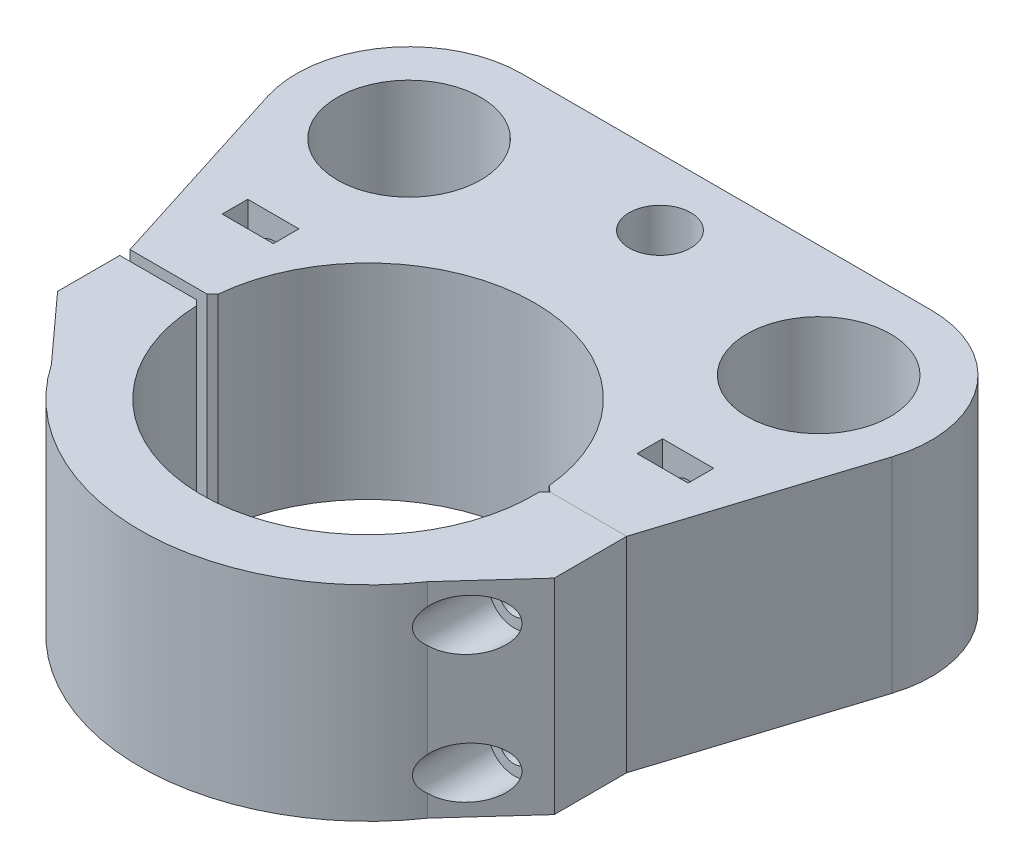
SolidWorks part; units mm, degrees
note: The reader was unsure of these and kept them because the rebuilt part matched: shared geometry of "Sketch1<3>", "Sketch2<3>".
material "6061-T4 (SS)"
ref_plane "Front Plane" through (0, 0, 0) normal (0, 0, 1) x (1, 0, 0)
ref_plane "Top Plane" through (0, 0, 0) normal (0, 1, 0) x (1, 0, 0)
ref_plane "Right Plane" through (0, 0, 0) normal (1, 0, 0) x (0, 0, -1)
sketch "Sketch1" plane through (0, 0, 0) normal (0, 1, 0) x (1, 0, 0)
  line L0 (-40, 48) -> (40, 48) construction
  line L1 (0, 48) -> (0, 0) construction
  line L2 (-40, 70) -> (40, 70)
  line L5 (0, 48) -> (0, 70) construction
  line L9 (0, 0) -> (0, -44.5) construction
  line L10 (48.5, 2) -> (60.972, 41.3535)
  line L12 (-48.5, 2) -> (-60.972, 41.3535)
  line L17 (-32.5, 0) -> (32.5, 0) construction
  line L18 (-32.5, 0) -> (-48.5, 0)
  line L19 (-32.4384, 2) -> (-48.5, 2)
  line L20 (32.5, 0) -> (48.5, 0)
  line L21 (32.4384, 2) -> (48.5, 2)
  line L22 (-48.5, 0) -> (-48.5, -12)
  line L23 (-48.5, -12) -> (-42.8515, -12)
  line L24 (48.5, 0) -> (48.5, -12)
  line L25 (48.5, -12) -> (42.8515, -12)
  line L26 (48.5, 2) -> (48.5, 0)
  arc A0 (-32.5, 0) -> (32.5, 0) centre (0, 0) ccw
  circle A2 centre (40, 48) radius 14
  circle A3 centre (-40, 48) radius 14
  arc A6 (-40, 70) -> (-60.972, 41.3535) centre (-40, 48) ccw
  circle A7 centre (0, 57) radius 6
  arc A8 (60.972, 41.3535) -> (40, 70) centre (40, 48) ccw
  arc A9 (32.4384, 2) -> (-32.4384, 2) centre (0, 0) ccw
  arc A10 (32.5, 0) -> (32.4384, 2) centre (0, 0) ccw
  arc A12 (-42.8515, -12) -> (42.8515, -12) centre (0, 0) ccw
  point P19 (0, -32.5)
  dimension "D1" = 65
  dimension "D2" = 12
  dimension "D4" = 28
  dimension "D6" = 22
  dimension "D7" = 8
  dimension "D8" = 12
  dimension "D9" = 13
  dimension "D3" = 80
  dimension "D5" = 48
  dimension "D10" = 2
  dimension "D11" = 12
  dimension "D12" = 16
extrude "Boss-Extrude1" add sketch "Sketch1" along normal blind 40
extrude "Boss-Extrude2" add sketch "Sketch1<3>" along normal through all separate body
sketch "Sketch1<3>" plane through (0, 0, 0) normal (0, 1, 0) x (1, 0, 0) same geometry as "Sketch1"
ref_plane "Plane2" through (0, 0, 12) normal (0, 0, -1) x (-1, 0, 0)
chamfer "Chamfer1" distance 9 distance2 18 2 edges at (-42.8515, 20, 12) (42.8515, 20, 12)
sketch "Sketch2" plane through (0, 0, 12) normal (0, 0, 1) x (1, 0, 0)
  line L0 (-48.5, 20) -> (-32.5, 20) construction
  line L3 (-40.5, 32.5) -> (-40.5, 7.5) construction
  line L7 (-32.5, 40) -> (-32.5, 0) construction
  line L9 (-48.5, 40) -> (-48.5, 0) construction
  line L10 (-36.7467, 0) -> (36.7467, 0) construction
  line L16 (0, 0) -> (0, 40) construction
  line L18 (-32.5, 40) -> (-32.5, 0) construction
  line L19 (36.7467, 40) -> (-36.7467, 40) construction
  line L20 (40.5, 32.5) -> (40.5, 7.5) construction
  line L21 (48.5, 20) -> (32.5, 20) construction
  line L22 (32.5, 40) -> (32.5, 0) construction
  circle A3 centre (-40.5, 32.5) radius 3
  circle A4 centre (-40.5, 7.5) radius 3
  circle A5 centre (40.5, 7.5) radius 3
  circle A6 centre (40.5, 32.5) radius 3
  circle A9 centre (-40.5, 32.5) radius 5
  circle A10 centre (-40.5, 7.5) radius 5
  circle A11 centre (40.5, 7.5) radius 5
  circle A12 centre (40.5, 32.5) radius 5
  point P2 (-40.5, 20)
  point P8 (-40.5, 7.5)
  point P10 (-40.5, 32.5)
  point P45 (40.5, 20)
  dimension "D4" = 6
  dimension "D1" = 10
  dimension "D2" = 25
extrude "Cut-Extrude1" cut sketch "Sketch2" along normal blind 78.1 contours A9 A3 | A10 A4 | A12 A6 | A11 A5 | A6
extrude "Cut-Extrude2" cut sketch "Sketch2<3>" against normal blind 35 and the other way through all contours A5 | A3 | A4 | A6
sketch "Sketch2<3>" plane through (0, 0, 12) normal (0, 0, 1) x (1, 0, 0) same geometry as "Sketch2"
ref_plane "Plane3" through (0, 0, -17) normal (0, 0, 1) x (1, 0, 0)
sketch "Sketch3" plane through (0, 0, -17) normal (0, 0, 1) x (1, 0, 0)
  line L0 (-45.5, 37.5) -> (-45.5, 55.0558)
  line L1 (-45.5, 37.5) -> (-35.5, 37.5) construction
  line L2 (-45.5, 37.5) -> (-45.5, 27.5)
  line L3 (-45.5, 27.5) -> (-35.5, 27.5)
  line L4 (-35.5, 37.5) -> (-35.5, 27.5)
  line L5 (-45.5, 37.5) -> (-35.5, 27.5) construction
  line L6 (-45.5, 27.5) -> (-35.5, 37.5) construction
  line L7 (-45.5, 2.5) -> (-35.5, 2.5) construction
  line L8 (-45.5, 2.5) -> (-45.5, 12.5)
  line L9 (-45.5, 12.5) -> (-35.5, 12.5)
  line L10 (-35.5, 2.5) -> (-35.5, 12.5)
  line L11 (0, 0) -> (0, 40) construction
  line L12 (-45.5, 12.5) -> (-35.5, 2.5) construction
  line L13 (-45.5, 55.0558) -> (-35.5, 55.0558)
  line L14 (-35.5, 55.0558) -> (-35.5, 37.5)
  line L15 (-45.5, 2.5) -> (-45.5, -15.7337)
  line L16 (-45.5, -15.7337) -> (-35.5, -15.7337)
  line L17 (-35.5, -15.7337) -> (-35.5, 2.5)
  line L18 (36.7467, 40) -> (-36.7467, 40) construction
  line L19 (45.5, 12.5) -> (35.5, 2.5) construction
  line L20 (45.5, 2.5) -> (35.5, 2.5) construction
  line L21 (45.5, 27.5) -> (35.5, 37.5) construction
  line L22 (45.5, 37.5) -> (35.5, 27.5) construction
  line L23 (45.5, 37.5) -> (35.5, 37.5) construction
  line L24 (35.5, -15.7337) -> (35.5, 2.5)
  line L25 (45.5, -15.7337) -> (35.5, -15.7337)
  line L26 (45.5, 2.5) -> (45.5, -15.7337)
  line L27 (35.5, 55.0558) -> (35.5, 37.5)
  line L28 (45.5, 55.0558) -> (35.5, 55.0558)
  line L29 (35.5, 2.5) -> (35.5, 12.5)
  line L30 (45.5, 12.5) -> (35.5, 12.5)
  line L31 (45.5, 2.5) -> (45.5, 12.5)
  line L32 (35.5, 37.5) -> (35.5, 27.5)
  line L33 (45.5, 27.5) -> (35.5, 27.5)
  line L34 (45.5, 37.5) -> (45.5, 27.5)
  line L35 (45.5, 37.5) -> (45.5, 55.0558)
  circle A0 centre (-40.5, 7.5) radius 3 construction
  point P0 (-40.5, 7.5)
  point P3 (-40.5, 32.5)
  point P35 (40.5, 32.5)
  point P36 (40.45, 7.5)
  dimension "D1" = 10
extrude "Cut-Extrude3" cut sketch "Sketch3" against normal blind 5
chamfer "Chamfer2" distance 1 angle 45 2 edges at (32.4384, 20, -2) (-32.4384, 20, -2)
chamfer "Chamfer3" distance 1 angle 45 2 edges at (-32.5, 20, 0) (32.4384, 20, -2)
